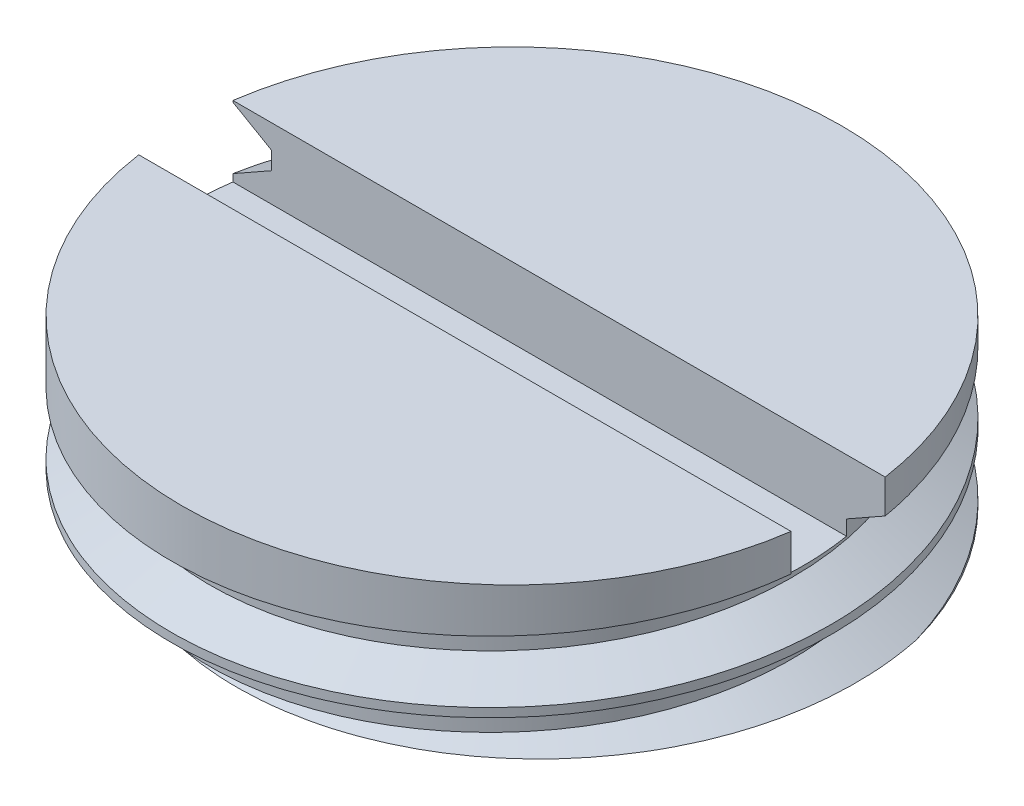
SolidWorks part; units mm, degrees
ref_plane "Спереди" through (0, 0, 0) normal (0, 0, 1) x (1, 0, 0)
ref_plane "Сверху" through (0, 0, 0) normal (0, 1, 0) x (1, 0, 0)
ref_plane "Справа" through (0, 0, 0) normal (1, 0, 0) x (0, 0, -1)
sketch "Эскиз1" plane through (0, 0, 0) normal (0, 1, 0) x (1, 0, 0)
  circle A0 centre (0, 0) radius 7
  dimension "D1" = 14
extrude "Бобышка-Вытянуть1" add sketch "Эскиз1" along normal blind 3.5
thread "Резьба1" pitch 1.5 method cut profile "Профиль резьбы1" start angle 0, offset 0, length 3.5, pitch 1.5, diameter 14
ref_plane "Плоскость1" through (-7, 3.5, 0) normal (0, 0, 1) x (-1, 0, 0)
sketch "Профиль резьбы1" plane through (-7, 3.5, 0) normal (0, 0, 1) x (-1, 0, 0)
  line L0 (0, 0) -> (0, 1.5) construction
  line L11 (0, 0) -> (0, 1.3125)
  line L12 (0, 1.3125) -> (-0.8119, 0.8437)
  line L13 (-0.8119, 0.8437) -> (-0.8119, 0.4687)
  line L15 (-0.8119, 0.4687) -> (0, 0)
  line L17 (-0.8119, 0.6562) -> (0, 0.6562) construction
  point P2 (0, 0)
  dimension "Pitch" = 1.5
  dimension "Profile_Angle" = 60
  dimension "Profile_Land" = 0.375
  dimension "Profile_Height" = 0.8119
sketch "Эскиз4" plane through (0, 0, 0) normal (1, 0, 0) x (0, 0, -1)
  line L0 (7, 3.5) -> (-7, 3.5) construction
  line L1 (-1, 3.5) -> (1, 3.5)
  line L2 (-1, 3.5) -> (-1, 2)
  line L3 (-1, 2) -> (1, 2)
  line L4 (1, 3.5) -> (1, 2)
  line L5 (0, 2) -> (0, 0) construction
  dimension "D1" = 1.5
  dimension "D2" = 2
extrude "Вырез-Вытянуть1" cut sketch "Эскиз4" against normal through all both and the other way through all
